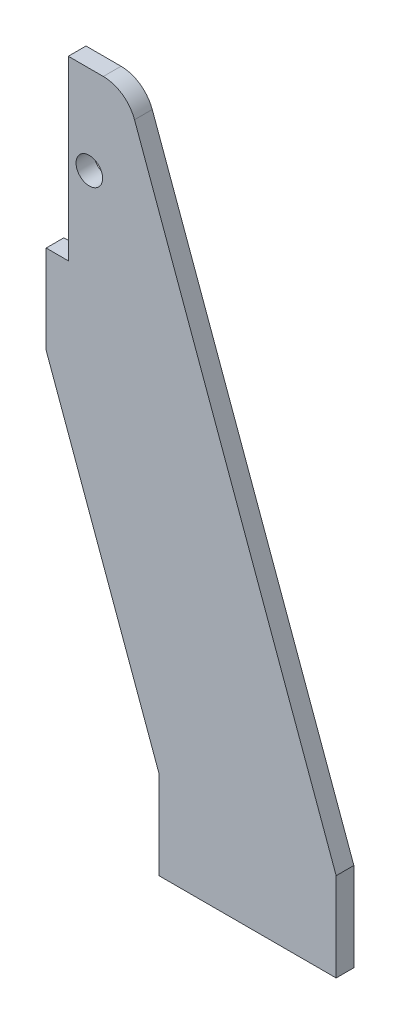
SolidWorks part; units mm, degrees
ref_plane "Alzado" through (0, 0, 0) normal (0, 0, 1) x (1, 0, 0)
ref_plane "Planta" through (0, 0, 0) normal (0, 1, 0) x (1, 0, 0)
ref_plane "Vista lateral" through (0, 0, 0) normal (1, 0, 0) x (0, 0, -1)
sketch "Croquis1" plane through (0, 0, 0) normal (0, 0, 1) x (1, 0, 0)
  line L0 (80, 0) -> (80, 40)
  line L1 (-40.9558, 300) -> (-25.1354, 300)
  line L2 (-50.9558, 220) -> (-50.9558, 180)
  line L3 (0, 0) -> (80, 0)
  line L4 (-11.04, 290.1303) -> (80, 40)
  line L7 (-50.9558, 220) -> (-40.9558, 220)
  line L8 (-40.9558, 300) -> (-40.9558, 220)
  line L9 (-50.9558, 180) -> (0, 40)
  line L11 (0, 40) -> (0, 0)
  arc A2 (-11.04, 290.1303) -> (-25.1354, 300) centre (-25.1354, 285) ccw
  dimension "D7" = 110
  dimension "D9" = 15
  dimension "D1" = 40
  dimension "D2" = 300
  dimension "D3" = 80
  dimension "D4" = 80
  dimension "D5" = 10
  dimension "D6" = 40
  dimension "D8" = 40
  dimension "D10" = 110
extrude "Saliente-Extruir1" add sketch "Croquis1" along normal blind 8
sketch "Croquis2" plane through (0, 0, 0) normal (0, 0, -1) x (-1, 0, 0)
  line L0 (25.1354, 300) -> (40.9558, 300) construction
  line L1 (40.9558, 300) -> (40.9558, 220) construction
  circle A0 centre (31.4558, 260) radius 6
  dimension "D3" = 12
  dimension "D1" = 40
  dimension "D2" = 9.5
extrude "Cortar-Extruir1" cut sketch "Croquis2" against normal through all
